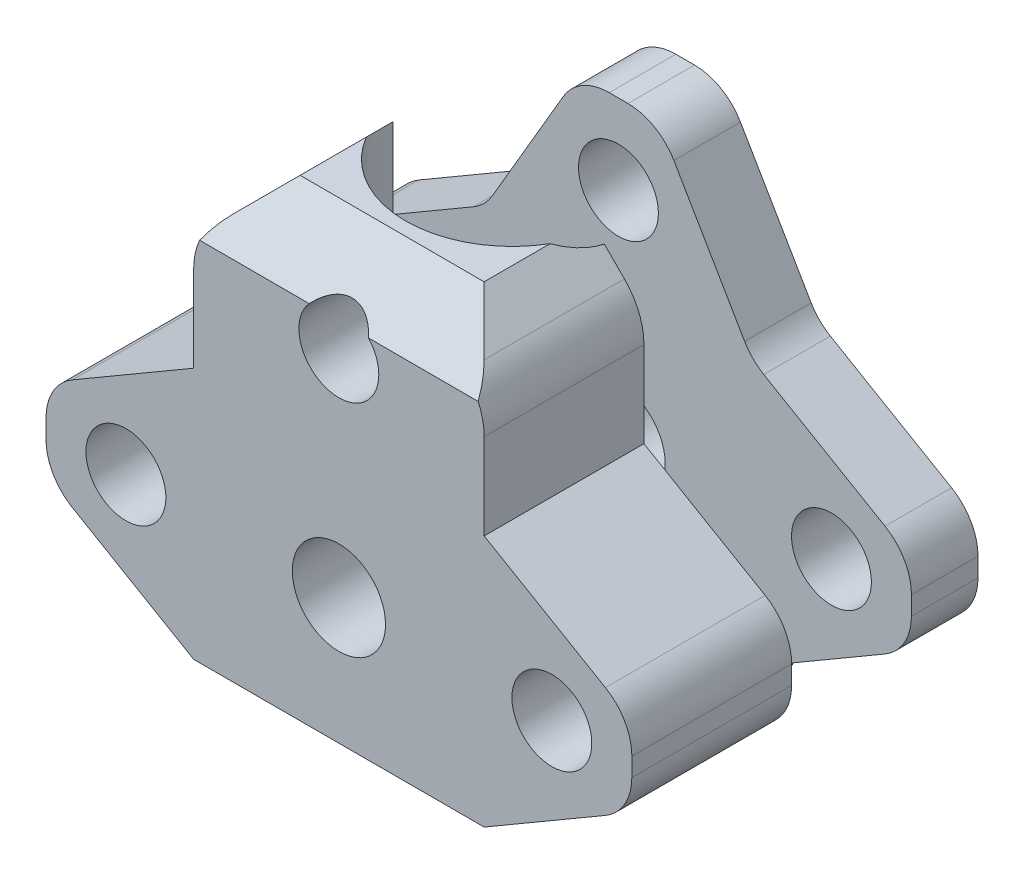
SolidWorks part; units mm, degrees
material "ABS"
ref_plane "Front Plane" through (0, 0, 0) normal (0, 0, 1) x (1, 0, 0)
ref_plane "Top Plane" through (0, 0, 0) normal (0, 1, 0) x (1, 0, 0)
ref_plane "Right Plane" through (0, 0, 0) normal (1, 0, 0) x (0, 0, -1)
sketch "Sketch1" plane through (0, 0, 0) normal (0, 0, 1) x (1, 0, 0)
  line L0 (0, 14.8318) -> (0, -14.8318)
  line L1 (-5, 14.8318) -> (-5, -14.8318)
  line L2 (5, 14.8318) -> (5, -14.8318)
  line L3 (-12.5, 0) -> (0, -12.5)
  line L4 (-12.5, 0) -> (0, 12.5)
  line L5 (0, -12.5) -> (12.5, 0)
  line L6 (0, 12.5) -> (12.5, 0)
  line L7 (-12.5, 0) -> (12.5, 0) construction
  line L8 (0, -12.5) -> (0, 12.5) construction
  line L9 (-10.9858, 11.0142) -> (11.0142, 10.9858)
  line L10 (-10.9858, 11.0142) -> (-11.0142, -10.9858)
  line L11 (11.0142, 10.9858) -> (10.9858, -11.0142)
  line L12 (-11.0142, -10.9858) -> (10.9858, -11.0142)
  line L13 (-10.9858, 11.0142) -> (10.9858, -11.0142) construction
  line L14 (11.0142, 10.9858) -> (-11.0142, -10.9858) construction
  circle A0 centre (0, 0) radius 8
  circle A1 centre (-8, 0) radius 1.5
  circle A2 centre (-0.0028, 8) radius 1.5
  circle A3 centre (7.9972, 0.0028) radius 1.5
  circle A4 centre (0, -7.9972) radius 1.5
  point P14 (-0.0014, 0.0014)
  point P15 (0, 0)
  dimension "D2" = 3
  dimension "D3" = 16
  dimension "D6" = 25
  dimension "D7" = 22
  dimension "D4" = 5
  dimension "D5" = 5
  dimension "D1" = 4
extrude "Boss-Extrude1" add sketch "Sketch1" along normal blind 2.5 contours A1 A0 L1 L4 L10 L3 | A2 L0 L9 L4 L1 A0 | A2 A0 L2 L6 L9 L0 | A3 A0 L2 L5 L11 L6 | A4 A0 L1 L3 L12 L0 | A4 L0 L12 L5 L2 A0 | A4 L0 A2 A0 L1 | A1 A0 L1 | A4 A0 L2 A2 L0 | A3 A0 L2
sketch "Sketch2" plane through (0, 0, 2.5) normal (0, 0, 1) x (1, 0, 0)
  line L4 (-5, -5) -> (5, 5) construction
  line L5 (5, -5) -> (-5, 5) construction
  line L6 (-5, 5) -> (-10.9981, 1.5019)
  line L7 (-5, -5) -> (5, -5)
  line L8 (-5, -5) -> (-5, 5)
  line L9 (-5, 5) -> (5, 5)
  line L10 (5, -5) -> (5, 5)
  line L11 (-5, -5) -> (5, 5) construction
  line L12 (-5, 5) -> (5, -5) construction
  line L13 (-5, 5) -> (-1.498, 11.002)
  line L14 (-1.498, 11.002) -> (1.5019, 10.9981)
  line L15 (1.5019, 10.9981) -> (5, 5)
  line L16 (5, 5) -> (11.002, 1.498)
  line L17 (-11.002, -1.498) -> (-5, -5)
  line L18 (-5, -5) -> (-1.5019, -10.9981)
  line L19 (1.498, -11.002) -> (5, -5)
  line L20 (10.9981, -1.5019) -> (5, -5)
  line L25 (1.498, -11.002) -> (10.9981, -1.5019)
  line L26 (10.9981, -1.5019) -> (11.002, 1.498)
  line L27 (11.002, 1.498) -> (1.5019, 10.9981)
  line L28 (1.5019, 10.9981) -> (-1.498, 11.002)
  line L29 (-1.498, 11.002) -> (-10.9981, 1.5019)
  line L30 (-10.9981, 1.5019) -> (-11.002, -1.498)
  line L31 (-11.002, -1.498) -> (-1.5019, -10.9981)
  line L32 (-1.5019, -10.9981) -> (1.498, -11.002)
  line L33 (1.498, -11.002) -> (10.9981, -1.5019)
  line L34 (10.9981, -1.5019) -> (11.002, 1.498)
  line L35 (11.002, 1.498) -> (1.5019, 10.9981)
  line L36 (1.5019, 10.9981) -> (-1.498, 11.002)
  line L37 (-1.498, 11.002) -> (-10.9981, 1.5019)
  line L38 (-10.9981, 1.5019) -> (-11.002, -1.498)
  line L39 (-11.002, -1.498) -> (-1.5019, -10.9981)
  line L40 (-1.5019, -10.9981) -> (1.498, -11.002)
  point P0 (0, 0)
  line M18 (1.498, -11.002) -> (10.9981, -1.5019)
  line M20 (11.002, 1.498) -> (1.5019, 10.9981)
  line M22 (-1.498, 11.002) -> (-10.9981, 1.5019)
  line M24 (-11.002, -1.498) -> (-1.5019, -10.9981)
  dimension "D1" = 10
  dimension "D2" = 0
extrude "Cut-Extrude1" cut sketch "Sketch2" against normal blind 2.5 contours L6 L13 M22 | L18 L17 M24 | L15 L16 M20 | L20 L19 M18
sketch "Sketch3" plane through (0, 0, 2.5) normal (0, 0, 1) x (1, 0, 0)
  circle A0 centre (0, 0) radius 1.75
  dimension "D1" = 3.5
extrude "Cut-Extrude2" cut sketch "Sketch3" against normal blind 2.5
fillet "Fillet1" radius 2 12 edges at (-10.9981, 1.5019, 1.25) (-5, 5, 1.25) (-1.498, 11.002, 1.25) (1.5019, 10.9981, 1.25) (5, 5, 1.25) (11.002, 1.498, 1.25) (10.9981, -1.5019, 1.25) (5, -5, 1.25) (1.498, -11.002, 1.25) (-1.5019, -10.9981, 1.25) (-5, -5, 1.25) (-11.002, -1.498, 1.25)
sketch "Sketch4" plane through (0, 0, 0) normal (0, 0, 1) x (1, 0, 0)
  line L0 (-5.4546, 4.7349) -> (5.4546, 4.7348)
  line L1 (-5.4546, -4.7348) -> (5.4546, -4.7349)
  line L12 (-5.4546, 4.7349) -> (-10.0071, 2.0798)
  line L13 (-10.9996, 0.3548) -> (-11.0005, -0.3477)
  line L14 (-10.0084, -2.0778) -> (-5.4546, -4.7348)
  line L15 (-4.7349, -5.4546) -> (-2.0798, -10.0071)
  line L16 (-0.3548, -10.9996) -> (0.3477, -11.0005)
  line L17 (2.0778, -10.0084) -> (4.7348, -5.4546)
  line L18 (5.4546, -4.7349) -> (10.0071, -2.0798)
  line L19 (10.9996, -0.3548) -> (11.0005, 0.3477)
  line L20 (10.0084, 2.0778) -> (5.4546, 4.7348)
  line L21 (4.7349, 5.4546) -> (2.0798, 10.0071)
  line L22 (0.3548, 10.9996) -> (-0.3477, 11.0005)
  line L23 (-2.0778, 10.0084) -> (-4.7348, 5.4546)
  line L24 (-5.4546, 4.7349) -> (-10.0071, 2.0798)
  line L25 (-10.9996, 0.3548) -> (-11.0005, -0.3477)
  line L26 (-10.0084, -2.0778) -> (-5.4546, -4.7348)
  line L27 (-4.7349, -5.4546) -> (-2.0798, -10.0071)
  line L28 (-0.3548, -10.9996) -> (0.3477, -11.0005)
  line L29 (2.0778, -10.0084) -> (4.7348, -5.4546)
  line L30 (5.4546, -4.7349) -> (10.0071, -2.0798)
  line L31 (10.9996, -0.3548) -> (11.0005, 0.3477)
  line L32 (10.0084, 2.0778) -> (5.4546, 4.7348)
  line L33 (4.7349, 5.4546) -> (2.0798, 10.0071)
  line L34 (0.3548, 10.9996) -> (-0.3477, 11.0005)
  line L35 (-2.0778, 10.0084) -> (-4.7348, 5.4546)
  circle A0 centre (-8, 0) radius 1.5 construction
  circle A1 centre (0, 0) radius 1.75
  circle A2 centre (0, 0) radius 1.75
  circle A3 centre (7.9972, 0.0028) radius 1.5
  circle A4 centre (7.9972, 0.0028) radius 1.5
  circle A5 centre (-0.0028, 8) radius 1.5
  circle A6 centre (-0.0028, 8) radius 1.5
  circle A7 centre (0, -7.9972) radius 1.5
  circle A8 centre (0, -7.9972) radius 1.5
  circle A9 centre (-8, 0) radius 1.5
  arc A12 (-10.0071, 2.0798) -> (-10.9996, 0.3548) centre (-8.9996, 0.3522) ccw
  arc A13 (-11.0005, -0.3477) -> (-10.0084, -2.0778) centre (-9.0005, -0.3503) ccw
  arc A14 (-4.7349, -5.4546) -> (-5.4546, -4.7348) centre (-6.4625, -6.4622) ccw
  arc A15 (-2.0798, -10.0071) -> (-0.3548, -10.9996) centre (-0.3522, -8.9996) ccw
  arc A16 (0.3477, -11.0005) -> (2.0778, -10.0084) centre (0.3503, -9.0005) ccw
  arc A17 (5.4546, -4.7349) -> (4.7348, -5.4546) centre (6.4622, -6.4625) ccw
  arc A18 (10.0071, -2.0798) -> (10.9996, -0.3548) centre (8.9996, -0.3522) ccw
  arc A19 (11.0005, 0.3477) -> (10.0084, 2.0778) centre (9.0005, 0.3503) ccw
  arc A20 (4.7349, 5.4546) -> (5.4546, 4.7348) centre (6.4625, 6.4622) ccw
  arc A21 (2.0798, 10.0071) -> (0.3548, 10.9996) centre (0.3522, 8.9996) ccw
  arc A22 (-0.3477, 11.0005) -> (-2.0778, 10.0084) centre (-0.3503, 9.0005) ccw
  arc A23 (-5.4546, 4.7349) -> (-4.7348, 5.4546) centre (-6.4622, 6.4625) ccw
  arc A24 (-10.0071, 2.0798) -> (-10.9996, 0.3548) centre (-8.9996, 0.3522) ccw
  arc A25 (-11.0005, -0.3477) -> (-10.0084, -2.0778) centre (-9.0005, -0.3503) ccw
  arc A26 (-4.7349, -5.4546) -> (-5.4546, -4.7348) centre (-6.4625, -6.4622) ccw
  arc A27 (-2.0798, -10.0071) -> (-0.3548, -10.9996) centre (-0.3522, -8.9996) ccw
  arc A28 (0.3477, -11.0005) -> (2.0778, -10.0084) centre (0.3503, -9.0005) ccw
  arc A29 (5.4546, -4.7349) -> (4.7348, -5.4546) centre (6.4622, -6.4625) ccw
  arc A30 (10.0071, -2.0798) -> (10.9996, -0.3548) centre (8.9996, -0.3522) ccw
  arc A31 (11.0005, 0.3477) -> (10.0084, 2.0778) centre (9.0005, 0.3503) ccw
  arc A32 (4.7349, 5.4546) -> (5.4546, 4.7348) centre (6.4625, 6.4622) ccw
  arc A33 (2.0798, 10.0071) -> (0.3548, 10.9996) centre (0.3522, 8.9996) ccw
  arc A34 (-0.3477, 11.0005) -> (-2.0778, 10.0084) centre (-0.3503, 9.0005) ccw
  arc A35 (-5.4546, 4.7349) -> (-4.7348, 5.4546) centre (-6.4622, 6.4625) ccw
  dimension "D1" = 0
  dimension "D2" = 0
  dimension "D3" = 0
  dimension "D4" = 0
  dimension "D5" = 0
extrude "Boss-Extrude2" add sketch "Sketch4" along normal blind 13 separate body contours L31 A31 L32 L0 L24 A24 L25 A25 L26 L1 L30 A30 A9 A4 A2
sketch "Sketch5" plane through (0, -4.7348, 0) normal (0, -1, 0) x (1, 0, 0)
  line L0 (10.0071, 0) -> (10.9996, 0) construction
  line L1 (10.9996, 0) -> (10.9996, 13) construction
  line L2 (10.9996, 13) -> (10.0071, 13) construction
  line L3 (5.4547, 0) -> (10.0071, 0) construction
  line L4 (-5.4546, 0) -> (5.4547, 0)
  line L5 (5.4547, 0) -> (5.4547, 13)
  line L6 (5.4547, 13) -> (-5.4546, 13)
  line L7 (-5.4546, 13) -> (-5.4546, 0)
  line L8 (-5.4546, 0) -> (5.4547, 0)
  line L9 (5.4547, 0) -> (5.4547, 13)
  line L10 (5.4547, 13) -> (-5.4546, 13)
  line L11 (-5.4546, 13) -> (-5.4546, 0)
  line L12 (10.0071, 13) -> (5.4547, 13) construction
  line L13 (5.4547, 13) -> (5.4547, 0) construction
  line L14 (-10.0084, 0) -> (-5.4546, 0) construction
  line L15 (-5.4546, 0) -> (-5.4546, 13) construction
  line L16 (-5.4546, 13) -> (-10.0084, 13) construction
  line L17 (-11.0005, 0) -> (-10.0084, 0) construction
  line L18 (-10.0084, 13) -> (-11.0005, 13) construction
  line L19 (-11.0005, 13) -> (-11.0005, 0) construction
  line L20 (10.0071, 0) -> (10.9996, 0)
  line L21 (10.9996, 0) -> (10.9996, 13)
  line L22 (10.9996, 13) -> (10.0071, 13)
  line L23 (5.4547, 0) -> (10.0071, 0)
  line L24 (10.0071, 13) -> (5.4547, 13)
  line L25 (5.4547, 13) -> (5.4547, 0)
  line L26 (-10.0084, 0) -> (-5.4546, 0)
  line L27 (-5.4546, 0) -> (-5.4546, 13)
  line L28 (-5.4546, 13) -> (-10.0084, 13)
  line L29 (-11.0005, 0) -> (-10.0084, 0)
  line L30 (-10.0084, 13) -> (-11.0005, 13)
  line L31 (-11.0005, 13) -> (-11.0005, 0)
  line L32 (-11.0005, 6.5) -> (10.9996, 6.5)
  line L33 (-11.0005, 6) -> (10.9996, 6)
  line L34 (-11.0005, 7) -> (10.9996, 7)
  line L36 (-11.0005, 7) -> (11.4754, 7)
  line L37 (-11.0005, 7) -> (-11.0005, -0.154)
  line L38 (-11.0005, -0.154) -> (11.4754, -0.154)
  line L39 (10.9996, 0) -> (11.0005, 0)
  line L40 (11.0005, 0) -> (11.0005, 13)
  line L41 (11.0005, 13) -> (10.9996, 13)
  line L42 (10.9996, 13) -> (10.9996, 0)
  line L43 (10.9996, 0) -> (11.0005, 0)
  line L44 (11.0005, 0) -> (11.0005, 13)
  line L45 (11.0005, 13) -> (10.9996, 13)
  line L46 (10.9996, 13) -> (10.9996, 0)
  line L47 (11.4754, 7) -> (11.4754, -0.154)
  circle A0 centre (-0.0005, 6.5) radius 4
  line M13 (-5.4546, 0) -> (5.4547, 0)
  line M14 (5.4547, 0) -> (5.4547, 13)
  line M16 (-5.4546, 13) -> (-5.4546, 0)
  dimension "D2" = 8
  dimension "D1" = 0
  dimension "D3" = 0.5
  dimension "D4" = 0.5
  dimension "D5" = 0
extrude "Cut-Extrude3" cut sketch "Sketch5" against normal blind 10 contours L34 A0 | A0 L33 M16 M13 M14 | L33 L31 L29 L26 M16 | L33 L23 L20 L21 M14 | L34 L25 L32 L21 | L25 L33 L21 L32 | A0 L32 L25 L34 | A0 L33 L25 L32 | L32 A0 L34 | L32 A0 L33 | A0 L34 L27 L32 | A0 L32 L27 L33 | L31 L33 L27 L32 | L34 L31 L32 L27 | L33 A0 | L47 L36 L44 L43 L20 L23 L26 L29 L37 L38 M13 | L43 L44 L36 L21
sketch "Sketch6" plane through (0, 4.7348, 0) normal (0, 1, 0) x (1, 0, 0)
  line L5 (-3.9691, -7) -> (-5.4547, -7)
  line L6 (-5.4547, -7) -> (-5.4547, -13)
  line L7 (-5.4547, -13) -> (5.4546, -13)
  line L8 (5.4546, -13) -> (5.4546, -7)
  line L9 (5.4546, -7) -> (3.9682, -7)
  line L10 (-3.9691, -7) -> (-5.4547, -7)
  line L11 (-5.4547, -7) -> (-5.4547, -13)
  line L12 (-5.4547, -13) -> (5.4546, -13)
  line L13 (5.4546, -13) -> (5.4546, -7)
  line L14 (5.4546, -7) -> (3.9682, -7)
  arc A1 (-3.9691, -7) -> (3.9682, -7) centre (-0.0005, -6.5) ccw
  arc A2 (-3.9691, -7) -> (3.9682, -7) centre (-0.0005, -6.5) ccw
  dimension "D1" = 0
extrude "Boss-Extrude3" add sketch "Sketch6" along normal up to surface (6.2731 mm away)
chamfer "Chamfer1" distance 2 angle 45 1 edges at (0, 11.0028, 13)
chamfer "Chamfer2" distance 2 angle 45 2 edges at (5.4546, 10.9958, 9) (-5.4546, 11.0099, 9)
fillet "Fillet3" radius 2.5 2 edges at (-5.4546, 9.0099, 10) (5.4546, 8.9958, 10)
sketch "Sketch8" plane through (0, 0, 13) normal (0, 0, 1) x (1, 0, 0)
  line L10 (5.2299, 8.9961) -> (-5.2302, 9.0096)
  line L11 (-5.4546, 7.9743) -> (-5.4546, 4.7349)
  line L12 (-5.4546, 4.7349) -> (-10.0071, 2.0798)
  line L13 (-10.9996, 0.3548) -> (-11.0005, -0.3477)
  line L14 (-10.0084, -2.0778) -> (-5.4546, -4.7348)
  line L15 (-5.4546, -4.7348) -> (5.4546, -4.7349)
  line L16 (5.4546, -4.7349) -> (10.0071, -2.0798)
  line L17 (10.9996, -0.3548) -> (11.0005, 0.3477)
  line L18 (10.0084, 2.0778) -> (5.4546, 4.7348)
  line L19 (5.4546, 4.7348) -> (5.4546, 7.9602)
  line L20 (5.2299, 8.9961) -> (-5.2302, 9.0096)
  line L21 (-5.4546, 7.9743) -> (-5.4546, 4.7349)
  line L22 (-5.4546, 4.7349) -> (-10.0071, 2.0798)
  line L23 (-10.9996, 0.3548) -> (-11.0005, -0.3477)
  line L24 (-10.0084, -2.0778) -> (-5.4546, -4.7348)
  line L25 (-5.4546, -4.7348) -> (5.4546, -4.7349)
  line L26 (5.4546, -4.7349) -> (10.0071, -2.0798)
  line L27 (10.9996, -0.3548) -> (11.0005, 0.3477)
  line L28 (10.0084, 2.0778) -> (5.4546, 4.7348)
  line L29 (5.4546, 4.7348) -> (5.4546, 7.9602)
  circle A1 centre (-0.0028, 8) radius 1.5
  arc A6 (-5.2302, 9.0096) -> (-5.4546, 7.9743) centre (-2.9546, 7.9743) ccw
  arc A7 (-10.0071, 2.0798) -> (-10.9996, 0.3548) centre (-8.9996, 0.3522) ccw
  arc A8 (-11.0005, -0.3477) -> (-10.0084, -2.0778) centre (-9.0005, -0.3503) ccw
  arc A9 (10.0071, -2.0798) -> (10.9996, -0.3548) centre (8.9996, -0.3522) ccw
  arc A10 (11.0005, 0.3477) -> (10.0084, 2.0778) centre (9.0005, 0.3503) ccw
  arc A11 (5.4546, 7.9602) -> (5.2299, 8.9961) centre (2.9546, 7.9603) ccw
  arc A12 (-5.2302, 9.0096) -> (-5.4546, 7.9743) centre (-2.9546, 7.9743) ccw
  arc A13 (-10.0071, 2.0798) -> (-10.9996, 0.3548) centre (-8.9996, 0.3522) ccw
  arc A14 (-11.0005, -0.3477) -> (-10.0084, -2.0778) centre (-9.0005, -0.3503) ccw
  arc A15 (10.0071, -2.0798) -> (10.9996, -0.3548) centre (8.9996, -0.3522) ccw
  arc A16 (11.0005, 0.3477) -> (10.0084, 2.0778) centre (9.0005, 0.3503) ccw
  arc A17 (5.4546, 7.9602) -> (5.2299, 8.9961) centre (2.9546, 7.9603) ccw
  dimension "D1" = 0
extrude "Cut-Extrude4" cut sketch "Sketch8" against normal blind 10.5 contours L20 A1 | L20 A1
